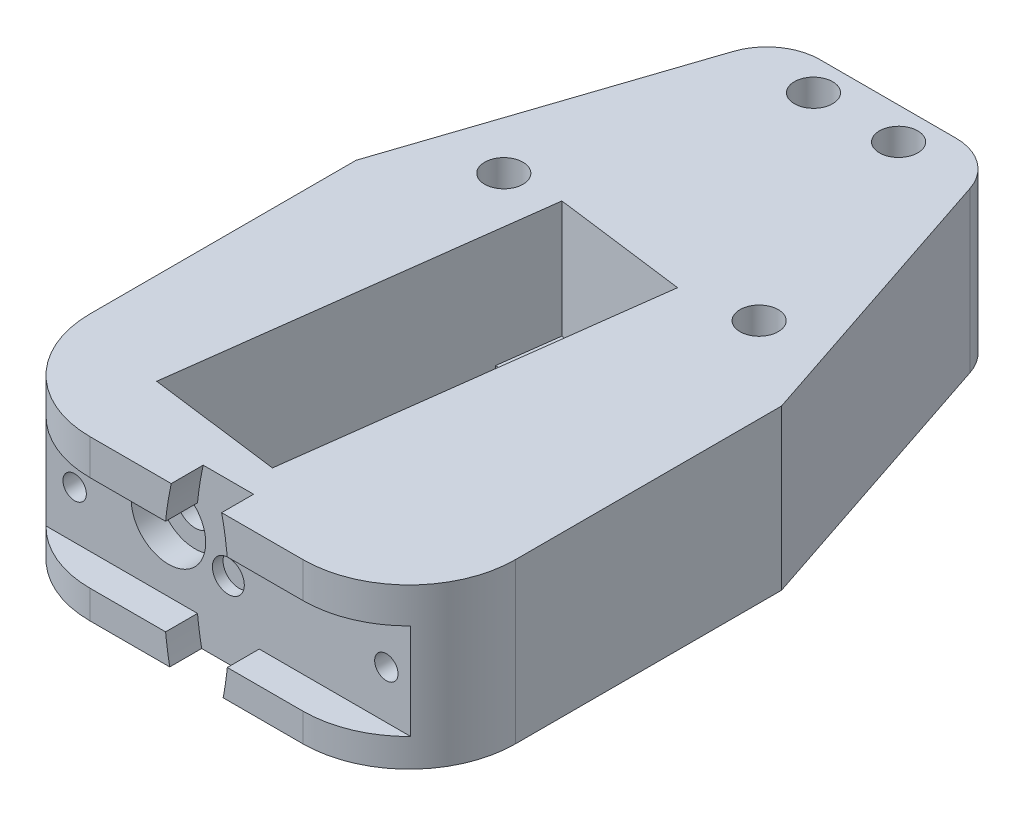
SolidWorks part; units mm, degrees
ref_plane "Front Plane" through (0, 0, 0) normal (0, 0, 1) x (1, 0, 0)
ref_plane "Top Plane" through (0, 0, 0) normal (0, 1, 0) x (1, 0, 0)
ref_plane "Right Plane" through (0, 0, 0) normal (1, 0, 0) x (0, 0, -1)
sketch "Sketch1" plane through (0, 0, 0) normal (0, 1, 0) x (1, 0, 0)
  line L0 (-10, 15) -> (-20, -15)
  line L1 (-10, 15) -> (10, 15)
  line L2 (-10, 15) -> (-10, -15)
  line L3 (-10, -15) -> (10, -15)
  line L4 (10, 15) -> (10, -15)
  line L5 (-10, 15) -> (10, -15) construction
  line L6 (-10, -15) -> (10, 15) construction
  line L7 (-20, -15) -> (-10, -15)
  line L8 (0, 15) -> (0, -15) construction
  line L9 (20, -15) -> (10, -15)
  line L10 (10, 15) -> (20, -15)
  line L11 (-20, -15) -> (-20, -50)
  line L12 (-20, -50) -> (20, -50)
  line L13 (20, -50) -> (20, -15)
  point P0 (0, 0)
  dimension "D1" = 30
  dimension "D2" = 20
  dimension "D3" = 10
  dimension "D4" = 65
extrude "Boss-Extrude1" add sketch "Sketch1" along normal blind 15 contours L0 L7 L2 | L4 L1 L2 L3 | L10 L4 L9 | L12 L13 L9 L3 L7 L11 region at (-13.3333, 0, 5) region at (0, 0, 0) region at (0, 0, 32.5) region at (13.3333, 0, 5)
sketch "Sketch2" plane through (0, 15, 0) normal (0, 1, 0) x (1, 0, 0)
  line L0 (0, 12.9693) -> (0, -9.9143) construction
  line L1 (1.8288, -38.4704) -> (-10.6669, -36.8525)
  line L2 (1.8288, -38.4704) -> (4.7693, -15.7599)
  line L3 (4.7693, -15.7599) -> (-7.7264, -14.142)
  line L4 (-10.6669, -36.8525) -> (-7.7264, -14.142)
  line L5 (-1.4786, -14.951) -> (-3.4374, -31.6376) construction
  line L6 (-10, 15) -> (10, 15) construction
  line L7 (-7.0138, -8.638) -> (-12.7325, -8.638) construction
  line L8 (-11.3795, -42.3565) -> (-7.0138, -8.638)
  line L9 (-7.0138, -8.638) -> (5.4819, -10.2559)
  line L10 (5.4819, -10.2559) -> (1.1162, -43.9744)
  line L11 (1.1162, -43.9744) -> (-11.3795, -42.3565)
  circle A0 centre (-3.4374, -31.6376) radius 2.3
  circle A1 centre (-4, 12) radius 1.8
  circle A2 centre (4, 12) radius 1.8
  circle A3 centre (12, -9.11) radius 1.8
  circle A4 centre (-12, -9.11) radius 1.8
  circle A5 centre (-12, -9.11) radius 12 construction
  circle A6 centre (-3.4374, -31.6376) radius 12.1 construction
  circle A7 centre (12, -9.11) radius 12 construction
  dimension "D3" = 4.6
  dimension "D7" = 3.6
  dimension "D12" = 24
  dimension "D13" = 24.2
  dimension "D16" = 24
  dimension "D17" = 5.55
  dimension "D1" = 22.9
  dimension "D2" = 12.6
  dimension "D4" = 6.1
  dimension "D5" = 34
  dimension "D6" = 5.55
  dimension "D8" = 4
  dimension "D9" = 3
  dimension "D10" = 12
  dimension "D11" = 24.11
  dimension "D14" = 6.1
  dimension "D15" = 90
extrude "Cut-Extrude1" cut sketch "Sketch2" against normal through all contours A4 | A3 | A1 | A2 region at (12, 15, 9.11) region at (-12, 15, 9.11)
fillet "Fillet2" radius 5 2 edges at (-10, 7.5, -15) (10, 7.5, -15)
extrude "Cut-Extrude2" cut sketch "Sketch2<3>" against normal through all contours L4 L1 L2 L3 A0 | A0 region at (-2.9189, 15, 25.9804) region at (-3.4374, 15, 31.6376)
sketch "Sketch2<3>" plane through (0, 15, 0) normal (0, 1, 0) x (1, 0, 0) same geometry as "Sketch2"
extrude "Cut-Extrude3" cut sketch "Sketch2<4>" against normal blind 11 contours L10 L9 L8 L3 | L11 L10 L1 L8 region at (-4.7754, 15, 40.4134) region at (-1.1223, 15, 12.199)
sketch "Sketch2<4>" plane through (0, 15, 0) normal (0, 1, 0) x (1, 0, 0) same geometry as "Sketch2"
sketch "Sketch3" plane through (0, 4, 0) normal (0, 1, 0) x (1, 0, 0)
  line L0 (-1.2937, -12.5045) -> (-4.8634, -40.0743) construction
  line L1 (-11.3795, -42.3565) -> (-7.0138, -8.638) construction
  line L2 (-1.2937, -12.5045) -> (5.037, -13.3241) construction
  line L4 (-4.8634, -40.0743) -> (1.4674, -40.894) construction
  line L6 (-7.0138, -8.638) -> (5.4819, -10.2559) construction
  line L7 (-7.0138, -8.638) -> (5.4819, -10.2559) construction
  line L8 (1.1162, -43.9744) -> (-11.3795, -42.3565) construction
  circle A0 centre (-1.2937, -12.5045) radius 1.2
  circle A1 centre (-4.8634, -40.0743) radius 1.2
  point P6 (-3.0785, -26.2894)
  dimension "D1" = 2.4
  dimension "D2" = 27.8
  dimension "D3" = 17
  dimension "D4" = 34
extrude "Cut-Extrude4" cut sketch "Sketch3" against normal blind 11
fillet "Fillet3" radius 10 2 edges at (20, 7.5, 50) (-20, 7.5, 50)
sketch "Sketch4" plane through (0, 0, 50) normal (0, 0, 1) x (1, 0, 0)
  line L0 (-3.13, 7.1631) -> (14.85, 7.1631) construction
  line L1 (19, 2.6631) -> (2.9011, 2.6631)
  line L2 (19, 2.6631) -> (19, 11.6631)
  line L3 (19, 11.6631) -> (2.9011, 11.6631)
  line L4 (-19, 2.6631) -> (-19, 11.6631)
  line L5 (19, 2.6631) -> (-19, 11.6631) construction
  line L6 (19, 11.6631) -> (-19, 2.6631) construction
  line L7 (-2.9011, 11.6631) -> (-19, 11.6631)
  line L8 (-2.9011, 2.6631) -> (-19, 2.6631)
  circle A1 centre (-14.45, 7.1631) radius 1.1
  circle A2 centre (14.85, 7.1631) radius 1.1
  circle A3 centre (0, 7.1631) radius 1.5
  ellipse E0 centre (0, 7.1631) end of major axis (0, 19.1499) minor radius 3.13 (-2.9011, 2.6631) -> (2.9011, 2.6631) ccw
  ellipse E2 centre (0, 7.1631) end of major axis (0, 19.1499) minor radius 3.13 (2.9011, 11.6631) -> (-2.9011, 11.6631) ccw
  point P0 (0, 7.1631)
  line M6 (-10, 0) -> (10, 0)
  line M7 (10, 0) -> (10, 15)
  line M8 (10, 15) -> (-10, 15)
  line M9 (-10, 15) -> (-10, 0)
  dimension "D5" = 2.2
  dimension "D6" = 3
  dimension "D1" = 9
  dimension "D2" = 38
  dimension "D3" = 14.45
  dimension "D4" = 14.85
extrude "Cut-Extrude5" cut sketch "Sketch4" against normal blind 3 contours A3 | E2 L7 L8 E0 L1 L3 A3 M8 M9 M6 M7 | L2 L3 L1 A2 M7 | L8 L7 L4 A1 M9 region at (14.5, 2.7904, 50) region at (6.4506, 2.9131, 50) region at (-14.5, 2.7904, 50) region at (0, 7.1631, 50)
extrude "Cut-Extrude6" cut sketch "Sketch4<2>" against normal blind 8 contours A1 | A2 region at (-14.45, 7.1631, 50)
sketch "Sketch4<2>" plane through (0, 0, 50) normal (0, 0, 1) x (1, 0, 0) same geometry as "Sketch4"
extrude "Cut-Extrude7" cut sketch "Sketch4<4>" against normal blind 4 contours A3 region at (0, 7.1631, 50)
sketch "Sketch4<4>" plane through (0, 0, 50) normal (0, 0, 1) x (1, 0, 0) same geometry as "Sketch4"
sketch "Sketch5" plane through (0, 4, 0) normal (0, 1, 0) x (1, 0, 0)
  line L0 (-10.6669, -36.8525) -> (1.8288, -38.4704)
  line L1 (-6.4025, -37.4046) -> (-6.6593, -39.388)
  line L2 (-6.6593, -39.388) -> (-2.6924, -39.9017)
  line L3 (-2.6924, -39.9017) -> (-2.4356, -37.9182)
  line L4 (-6.4025, -37.4046) -> (-2.4356, -37.9182)
  line L5 (-4.419, -37.6614) -> (-4.1024, -35.2162) construction
  point P10 (-4.6758, -39.6449)
  circle M6 centre (-4.8634, -40.0743) radius 1.2
  dimension "D1" = 4
  dimension "D2" = 2
extrude "Cut-Extrude8" cut sketch "Sketch5" against normal blind 4 contours L2 L3 L0 L4 L1 M6 region at (-4.5086, 4, 38.5344)
sketch "Sketch6" plane through (0, 0, 47) normal (0, 0, 1) x (1, 0, 0)
  line L0 (-5.6285, 15) -> (-5.6285, 7) construction
  line L1 (-10, 15) -> (-2.3684, 15) construction
  circle A0 centre (-5.6285, 8.8) radius 1.8
  circle A1 centre (-5.6285, 8.8) radius 3.5
  dimension "D2" = 3.6
  dimension "D3" = 7
  dimension "D1" = 8
extrude "Cut-Extrude9" cut sketch "Sketch6" against normal blind 2.5
extrude "Cut-Extrude10" cut sketch "Sketch6<2>" against normal blind 13.5 contours L0 A0 | A0 L0 region at (-4.8645, 8.8, 47) region at (-6.3924, 8.8, 47)
sketch "Sketch6<2>" plane through (0, 0, 47) normal (0, 0, 1) x (1, 0, 0) same geometry as "Sketch6"
